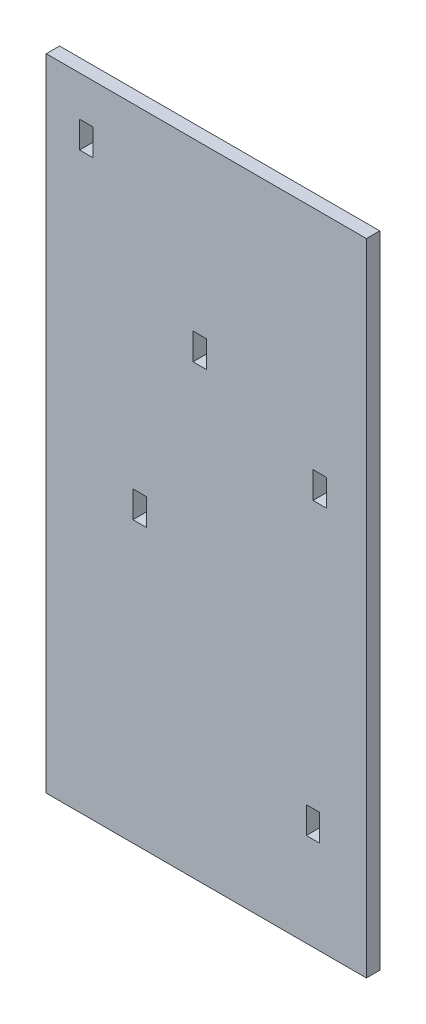
SolidWorks part; units mm, degrees
ref_plane "Front Plane" through (0, 0, 0) normal (0, 0, 1) x (1, 0, 0)
ref_plane "Top Plane" through (0, 0, 0) normal (0, 1, 0) x (1, 0, 0)
ref_plane "Right Plane" through (0, 0, 0) normal (1, 0, 0) x (0, 0, -1)
sketch "Sketch1" plane through (0, 0, 0) normal (0, 0, 1) x (1, 0, 0)
  line L1 (304.8, -609.6) -> (-304.8, -609.6)
  line L2 (304.8, -609.6) -> (304.8, 609.6)
  line L3 (304.8, 609.6) -> (-304.8, 609.6)
  line L4 (-304.8, -609.6) -> (-304.8, 609.6)
  line L5 (304.8, -609.6) -> (-304.8, 609.6) construction
  line L6 (304.8, 609.6) -> (-304.8, -609.6) construction
  point P0 (0, 0)
  dimension "D1" = 609.6
  dimension "D2" = 1219.2
extrude "Boss-Extrude1" add sketch "Sketch1" along normal mid plane 25.4
sketch "Sketch2" plane through (0, 0, -12.7) normal (0, 0, -1) x (-1, 0, 0)
  line L0 (304.8, -609.6) -> (-304.8, -609.6) construction
  line L1 (-228.6, 177.8) -> (-203.2, 177.8)
  line L2 (-228.6, 177.8) -> (-228.6, 127)
  line L3 (-228.6, 127) -> (-203.2, 127)
  line L4 (-203.2, 177.8) -> (-203.2, 127)
  line L5 (-228.6, 177.8) -> (-203.2, 127) construction
  line L6 (-228.6, 127) -> (-203.2, 177.8) construction
  line L7 (0, 292.1) -> (25.4, 292.1)
  line L8 (0, 292.1) -> (0, 241.3)
  line L9 (0, 241.3) -> (25.4, 241.3)
  line L10 (25.4, 292.1) -> (25.4, 241.3)
  line L11 (0, 292.1) -> (25.4, 241.3) construction
  line L12 (0, 241.3) -> (25.4, 292.1) construction
  line L13 (215.9, 533.4) -> (241.3, 533.4)
  line L14 (215.9, 533.4) -> (215.9, 482.6)
  line L15 (215.9, 482.6) -> (241.3, 482.6)
  line L16 (241.3, 533.4) -> (241.3, 482.6)
  line L17 (215.9, 533.4) -> (241.3, 482.6) construction
  line L18 (215.9, 482.6) -> (241.3, 533.4) construction
  line L19 (114.3, -25.4) -> (139.7, -25.4)
  line L20 (114.3, -25.4) -> (114.3, -76.2)
  line L21 (114.3, -76.2) -> (139.7, -76.2)
  line L22 (139.7, -25.4) -> (139.7, -76.2)
  line L23 (114.3, -25.4) -> (139.7, -76.2) construction
  line L24 (114.3, -76.2) -> (139.7, -25.4) construction
  line L25 (-215.9, -381) -> (-190.5, -381)
  line L26 (-215.9, -381) -> (-215.9, -431.8)
  line L27 (-215.9, -431.8) -> (-190.5, -431.8)
  line L28 (-190.5, -381) -> (-190.5, -431.8)
  line L29 (-215.9, -381) -> (-190.5, -431.8) construction
  line L30 (-215.9, -431.8) -> (-190.5, -381) construction
  line L31 (-304.8, -609.6) -> (-304.8, 609.6) construction
  line L32 (304.8, 609.6) -> (304.8, -609.6) construction
  line L33 (-304.8, 609.6) -> (304.8, 609.6) construction
  line L34 (-203.2, 152.4) -> (-228.6, 152.4)
  line L35 (25.4, 266.7) -> (0, 266.7)
  line L36 (241.3, 508) -> (215.9, 508)
  line L37 (139.7, -50.8) -> (114.3, -50.8)
  line L38 (-215.9, -406.4) -> (-190.5, -406.4)
  point P0 (-215.9, 152.4)
  point P5 (12.7, 266.7)
  point P10 (228.6, 508)
  point P15 (127, -50.8)
  point P20 (-203.2, -406.4)
  dimension "D1" = 50.8
  dimension "D2" = 25.4
  dimension "D3" = 50.8
  dimension "D4" = 25.4
  dimension "D5" = 50.8
  dimension "D6" = 25.4
  dimension "D7" = 25.4
  dimension "D8" = 50.8
  dimension "D9" = 50.8
  dimension "D10" = 25.4
  dimension "D11" = 203.2
  dimension "D12" = 101.6
  dimension "D13" = 177.8
  dimension "D14" = 558.8
  dimension "D15" = 88.9
  dimension "D16" = 457.2
  dimension "D17" = 317.5
  dimension "D18" = 317.5
  dimension "D19" = 76.2
  dimension "D20" = 101.6
extrude "Cut-Extrude1" cut sketch "Sketch2" against normal through all contours L35 L10 L7 L8 | L10 L35 L8 L9 | L4 L34 L2 L3 | L34 L4 L1 L2 | L37 L22 L19 L20 | L22 L37 L20 L21 | L16 L36 L14 L15 | L36 L16 L13 L14 | L38 L26 L27 L28 | L26 L38 L28 L25 region at (215.9, 165.1, -12.7) region at (215.9, 139.7, -12.7) region at (-12.7, 279.4, -12.7) region at (-12.7, 254, -12.7) region at (-228.6, 520.7, -12.7) region at (-228.6, 495.3, -12.7) region at (-127, -38.1, -12.7) region at (-127, -63.5, -12.7) region at (203.2, -393.7, -12.7) region at (203.2, -419.1, -12.7)
ref_axis "Axis1" through (228.6, 152.4, -12.7) along (-1, 0, 0)
ref_axis "Axis2" through (-25.4, 266.7, -12.7) along (1, 0, 0)
ref_axis "Axis3" through (-241.3, 508, -12.7) along (1, 0, 0)
ref_axis "Axis4" through (-139.7, -50.8, -12.7) along (1, 0, 0)
ref_axis "Axis5" through (190.5, -406.4, -12.7) along (1, 0, 0)
